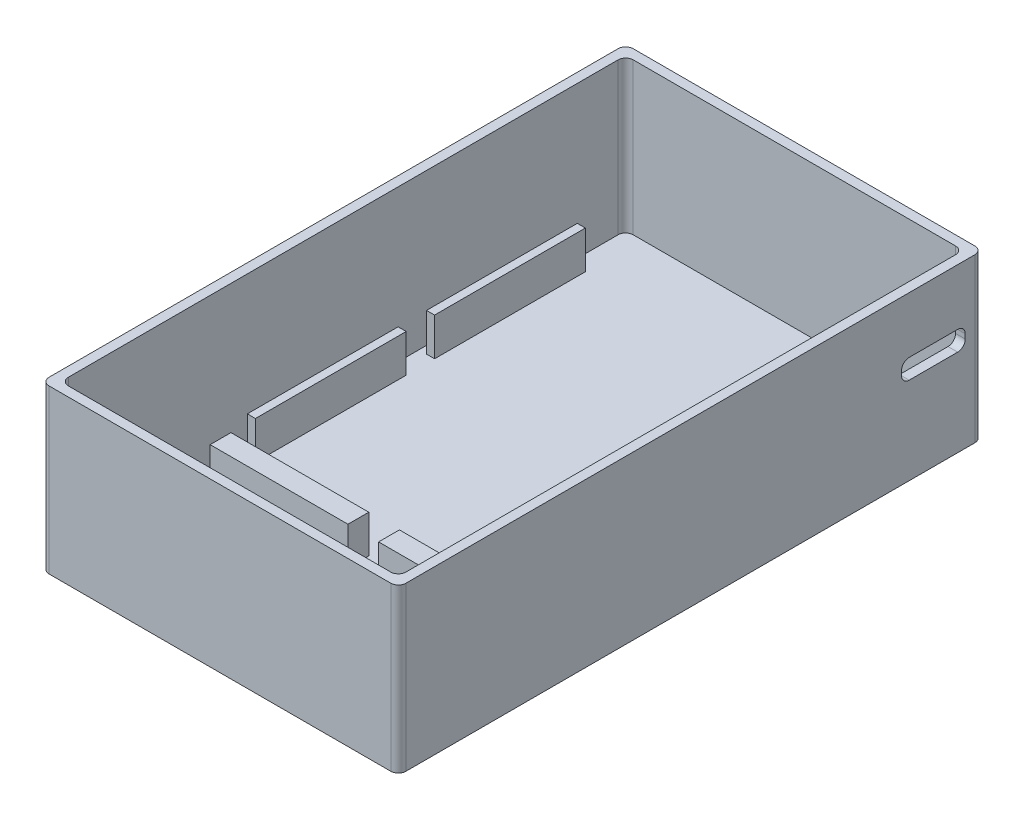
SolidWorks part; units mm, degrees
ref_plane "Front Plane" through (0, 0, 0) normal (0, 0, 1) x (1, 0, 0)
ref_plane "Top Plane" through (0, 0, 0) normal (0, 1, 0) x (1, 0, 0)
ref_plane "Right Plane" through (0, 0, 0) normal (1, 0, 0) x (0, 0, -1)
sketch "Sketch1" plane through (0, 0, 0) normal (0, 1, 0) x (1, 0, 0)
  line L5 (0, 0) -> (47.0912, 0)
  line L6 (0, 0) -> (0, -77.0912)
  line L7 (0, -77.0912) -> (47.0912, -77.0912)
  line L8 (47.0912, 0) -> (47.0912, -77.0912)
extrude "Boss-Extrude1" add sketch "Sketch1" along normal blind 1.5
sketch "Sketch2" plane through (0, 1.5, 0) normal (0, 1, 0) x (1, 0, 0)
  line L3 (1.2728, -1.2728) -> (45.8184, -1.2728)
  line L4 (1.2728, -1.2728) -> (1.2728, -75.8184)
  line L5 (1.2728, -75.8184) -> (45.8184, -75.8184)
  line L6 (45.8184, -1.2728) -> (45.8184, -75.8184)
  line L7 (0, 0) -> (47.0912, 0)
  line L8 (0, 0) -> (0, -77.0912)
  line L9 (0, -77.0912) -> (47.0912, -77.0912)
  line L10 (47.0912, 0) -> (47.0912, -77.0912)
extrude "Boss-Extrude2" add sketch "Sketch2" along normal blind 20
fillet "Fillet4" radius 1 8 edges at (45.8184, 11.5, 1.2728) (1.2728, 11.5, 1.2728) (45.8184, 11.5, 75.8184) (1.2728, 11.5, 75.8184) (47.0912, 10.75, 0) (0, 10.75, 0) (47.0912, 10.75, 77.0912) (0, 10.75, 77.0912)
sketch "Sketch3" plane through (0, 1.5, 0) normal (0, 1, 0) x (1, 0, 0)
  line L1 (2.2728, -2.2728) -> (44.8184, -2.2728)
  line L2 (2.2728, -2.2728) -> (2.2728, -74.8184)
  line L3 (2.2728, -74.8184) -> (44.8184, -74.8184)
  line L4 (44.8184, -2.2728) -> (44.8184, -74.8184)
sketch "Sketch9" plane through (47.0912, 0, 0) normal (1, 0, 0) x (0, 0, -1)
  line L1 (-10.6728, 11.5) -> (-2.2728, 11.5)
  line L2 (-10.6728, 11.5) -> (-10.6728, 14.1)
  line L3 (-10.6728, 14.1) -> (-2.2728, 14.1)
  line L4 (-2.2728, 11.5) -> (-2.2728, 14.1)
  line L6 (-2.2728, 11.5) -> (-10.3106, 11.5)
  point P0 (0, 0)
extrude "Cut-Extrude4" cut sketch "Sketch9" against normal blind 2 contours L1 L4 L3 L2 region at (47.0912, 12.8, 6.4728)
fillet "Fillet5" radius 1 4 edges at (46.4548, 14.1, 10.6728) (46.4548, 11.5, 2.2728) (46.4548, 14.1, 2.2728) (46.4548, 11.5, 10.6728)
sketch "Sketch10" plane through (0, 1.5, 0) normal (0, 1, 0) x (1, 0, 0)
  line L5 (3.3356, -58.1743) -> (21.5231, -58.1743)
  line L6 (3.3356, -58.1743) -> (3.3356, -55.4274)
  line L7 (3.3356, -55.4274) -> (21.5231, -55.4274)
  line L8 (21.5231, -58.1743) -> (21.5231, -55.4274)
  line L10 (25.5681, -58.1743) -> (25.5681, -55.4274)
  line L11 (43.7555, -55.4274) -> (25.5681, -55.4274)
  line L12 (43.7555, -58.1743) -> (43.7555, -55.4274)
  line L13 (43.7555, -58.1743) -> (25.5681, -58.1743)
  line L14 (2.2728, -2.2728) -> (2.2728, -74.8184) construction
  line L15 (3.3356, -52.1993) -> (2.2728, -52.1993)
  line L16 (3.3356, -52.1993) -> (3.3356, -32.3037)
  line L17 (3.3356, -32.3037) -> (2.2728, -32.3037)
  line L18 (2.2728, -52.1993) -> (2.2728, -32.3037)
  line L20 (2.2728, -8.6554) -> (2.2728, -28.551)
  line L21 (3.3356, -28.551) -> (2.2728, -28.551)
  line L22 (3.3356, -8.6554) -> (3.3356, -28.551)
  line L23 (3.3356, -8.6554) -> (2.2728, -8.6554)
  line L24 (43.7555, -8.6554) -> (44.8184, -8.6554)
  line L25 (43.7555, -8.6554) -> (43.7555, -28.551)
  line L26 (43.7555, -28.551) -> (44.8184, -28.551)
  line L27 (44.8184, -8.6554) -> (44.8184, -28.551)
  line L28 (44.8184, -52.1993) -> (44.8184, -32.3037)
  line L29 (43.7555, -32.3037) -> (44.8184, -32.3037)
  line L30 (43.7555, -52.1993) -> (43.7555, -32.3037)
  line L31 (43.7555, -52.1993) -> (44.8184, -52.1993)
extrude "Boss-Extrude4" add sketch "Sketch10" along normal blind 5
